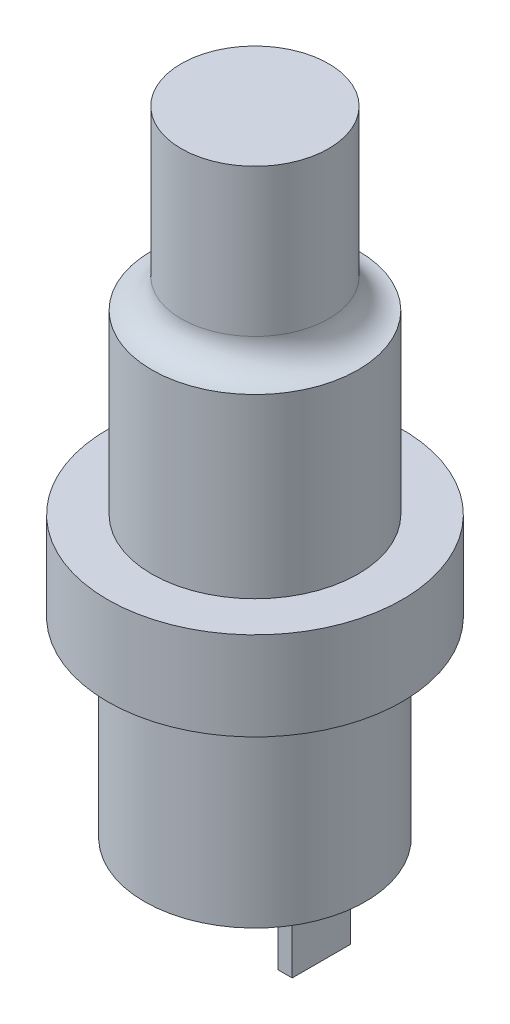
SolidWorks part; units mm, degrees
ref_plane "Спереди" through (0, 0, 0) normal (0, 0, 1) x (1, 0, 0)
ref_plane "Сверху" through (0, 0, 0) normal (0, 1, 0) x (1, 0, 0)
ref_plane "Справа" through (0, 0, 0) normal (1, 0, 0) x (0, 0, -1)
sketch "Эскиз1" plane through (0, 0, 0) normal (0, 1, 0) x (1, 0, 0)
  circle A0 centre (0, 0) radius 3.75
  dimension "D1" = 7.5
extrude "Бобышка-Вытянуть1" add sketch "Эскиз1" along normal blind 6.5
sketch "Эскиз2" plane through (0, 6.5, 0) normal (0, 1, 0) x (1, 0, 0)
  circle A0 centre (0, 0) radius 5
extrude "Бобышка-Вытянуть2" add sketch "Эскиз2" along normal blind 3
sketch "Эскиз3" plane through (0, 9.5, 0) normal (0, 1, 0) x (1, 0, 0)
  circle A0 centre (0, 0) radius 3.5
extrude "Бобышка-Вытянуть3" add sketch "Эскиз3" along normal blind 6
sketch "Эскиз4" plane through (0, 15.5, 0) normal (0, 1, 0) x (1, 0, 0)
  circle A0 centre (0, 0) radius 2.5
extrude "Бобышка-Вытянуть4" add sketch "Эскиз4" along normal blind 6
fillet "Скругление1" radius 1 1 edges at (0, 15.5, 2.5)
sketch "Эскиз5" plane through (0, 0, 0) normal (0, -1, 0) x (1, 0, 0)
  line L0 (-3.75, 0) -> (3.75, 0) construction
  line L1 (0, 3.75) -> (0, -3.75) construction
  line L2 (1.7664, 0.9857) -> (2.25, 0.9857)
  line L3 (1.7664, 0.9857) -> (1.7664, -0.9857)
  line L4 (1.7664, -0.9857) -> (2.25, -0.9857)
  line L5 (2.25, 0.9857) -> (2.25, -0.9857)
  line L6 (1.7664, 0.9857) -> (2.25, -0.9857) construction
  line L7 (1.7664, -0.9857) -> (2.25, 0.9857) construction
  line L8 (-1.7664, -0.9857) -> (-2.25, 0.9857) construction
  line L9 (-1.7664, 0.9857) -> (-2.25, -0.9857) construction
  line L10 (-2.25, 0.9857) -> (-2.25, -0.9857)
  line L11 (-1.7664, -0.9857) -> (-2.25, -0.9857)
  line L12 (-1.7664, 0.9857) -> (-1.7664, -0.9857)
  line L13 (-1.7664, 0.9857) -> (-2.25, 0.9857)
  circle A0 centre (0, 0) radius 3.75 construction
  circle A1 centre (0, 0) radius 3.75 construction
  point P7 (2.0082, 0)
  point P18 (-2.0082, 0)
  dimension "D1" = 1.5
extrude "Бобышка-Вытянуть5" add sketch "Эскиз5" along normal blind 2.5
